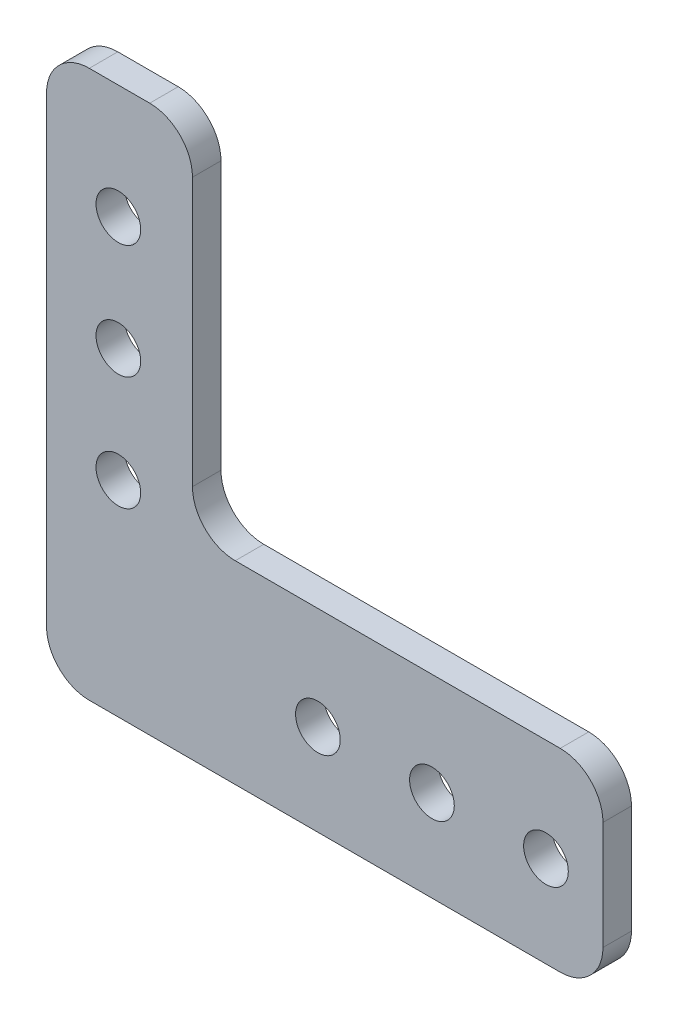
SolidWorks part; units mm, degrees
material "6061-T6 (SS)"
ref_plane "Front Plane" through (0, 0, 0) normal (0, 0, 1) x (1, 0, 0)
ref_plane "Top Plane" through (0, 0, 0) normal (0, 1, 0) x (1, 0, 0)
ref_plane "Right Plane" through (0, 0, 0) normal (1, 0, 0) x (0, 0, -1)
sketch "Sketch1" plane through (0, 0, 0) normal (0, 0, 1) x (1, 0, 0)
  line L1 (-34.925, -31.75) -> (34.925, -31.75)
  line L2 (-34.925, -31.75) -> (-34.925, 31.75)
  line L3 (-34.925, 31.75) -> (34.925, 31.75)
  line L4 (34.925, -31.75) -> (34.925, 31.75)
  line L5 (-34.925, -31.75) -> (34.925, 31.75) construction
  line L6 (-34.925, 31.75) -> (34.925, -31.75) construction
  line L7 (34.925, 31.75) -> (-10.795, 31.75)
  line L8 (34.925, 31.75) -> (34.925, -7.62)
  line L9 (34.925, -7.62) -> (-10.795, -7.62)
  line L10 (-10.795, 31.75) -> (-10.795, -7.62)
  line L11 (-34.925, -31.75) -> (-27.051, -31.75)
  line L12 (-34.925, -31.75) -> (-34.925, 31.75)
  line L13 (-34.925, 31.75) -> (-27.051, 31.75)
  line L14 (-27.051, -31.75) -> (-27.051, 31.75)
  line L15 (-27.051, -31.75) -> (34.925, -31.75)
  line L16 (-27.051, -31.75) -> (-27.051, -29.21)
  line L17 (-27.051, -29.21) -> (34.925, -29.21)
  line L18 (34.925, -31.75) -> (34.925, -29.21)
  circle A0 centre (-19.05, -19.05) radius 2.4892
  circle A1 centre (-19.05, -6.35) radius 2.4892
  circle A2 centre (-19.05, 6.35) radius 2.4892
  circle A3 centre (-19.05, 19.05) radius 2.4892
  circle A4 centre (3.175, -19.05) radius 2.4892
  circle A5 centre (15.875, -19.05) radius 2.4892
  circle A6 centre (28.575, -19.05) radius 2.4892
  point P0 (0, 0)
  dimension "D7" = 4.9784
  dimension "D14" = 22.225
  dimension "D1" = 69.85
  dimension "D2" = 63.5
  dimension "D3" = 24.13
  dimension "D4" = 24.13
  dimension "D5" = 7.874
  dimension "D6" = 63.5
  dimension "D8" = 15.875
  dimension "D9" = 12.7
  dimension "D10" = 12.7
  dimension "D11" = 12.7
  dimension "D12" = 12.7
  dimension "D13" = 12.7
  dimension "D15" = 12.7
  dimension "D16" = 2.54
extrude "Boss-Extrude1" add sketch "Sketch1" along normal blind 3.175 contours L14 L17 L4 L9 L10 L3 A6 A5 A4 A3 A2 A1 A0 | A0 region at (-3.4132, -8.582, 0) region at (-19.05, -19.05, 0)
fillet "Fillet1" radius 4.7625 6 edges at (-27.051, 31.75, 1.5875) (-10.795, 31.75, 1.5875) (-10.795, -7.62, 1.5875) (34.925, -7.62, 1.5875) (34.925, -29.21, 1.5875) (-27.051, -29.21, 1.5875)
